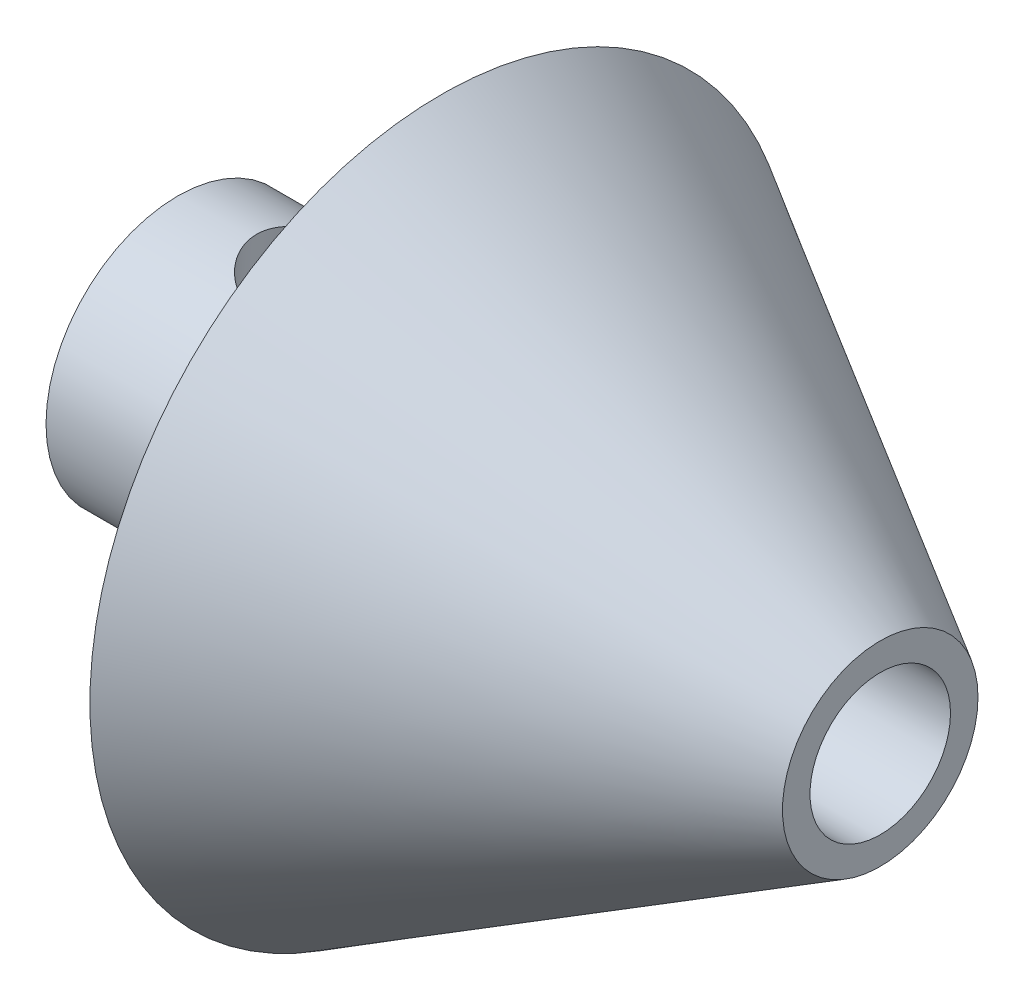
SolidWorks part; units mm, degrees
ref_plane "Alzado" through (0, 0, 0) normal (0, 0, 1) x (1, 0, 0)
ref_plane "Planta" through (0, 0, 0) normal (0, 1, 0) x (1, 0, 0)
ref_plane "Vista lateral" through (0, 0, 0) normal (1, 0, 0) x (0, 0, -1)
sketch "Croquis1" plane through (0, 0, 0) normal (1, 0, 0) x (0, 0, -1)
  line L0 (0, 7.5) -> (0, -7.5) construction
  line L1 (-7.5, 0) -> (7.5, 0) construction
  circle A0 centre (0, 0) radius 7.5
  dimension "D1" = 15
extrude "Saliente-Extruir1" add sketch "Croquis1" along normal blind 15
sketch "Croquis2" plane through (15, 0, 0) normal (1, 0, 0) x (0, 0, -1)
  circle A0 centre (0, 0) radius 20
  dimension "D1" = 40
extrude "Saliente-Extruir2" add sketch "Croquis2" along normal blind 25 draft 30
sketch "Croquis3" plane through (40, 0, 0) normal (1, 0, 0) x (0, 0, -1)
  circle A0 centre (0, 0) radius 4
  dimension "D1" = 8
extrude "Cortar-Extruir2" cut sketch "Croquis3" against normal blind 70
hole_wizard "Taladro de margen para 1/41" positions "Croquis3D1" profile "Croquis4" hole size "1/4" standard "Ansi Inch" end condition up to next
sketch3d "Croquis3D1"
  point P0 (7.5, 7.4812, -0.5307)
  dimension "D1" = 7.5
sketch "Croquis4" plane through (7.5, 7.4812, -0.5307) normal (1, 0, 0) x (0, 0.0708, 0.9975)
  line L0 (0, 0) -> (0, 3.5)
  line L1 (0, 3.5) -> (3.3782, 3.5)
  line L2 (3.3782, 3.5) -> (3.3782, 0)
  line L5 (3.3782, 0) -> (0, 0)
  line L11 (0, -6.35) -> (0, 107.95) construction
  dimension "Diámetro de taladro hasta el siguiente" = 6.7564
  dimension "Profundidad de taladro hasta el siguiente" = 3.5
